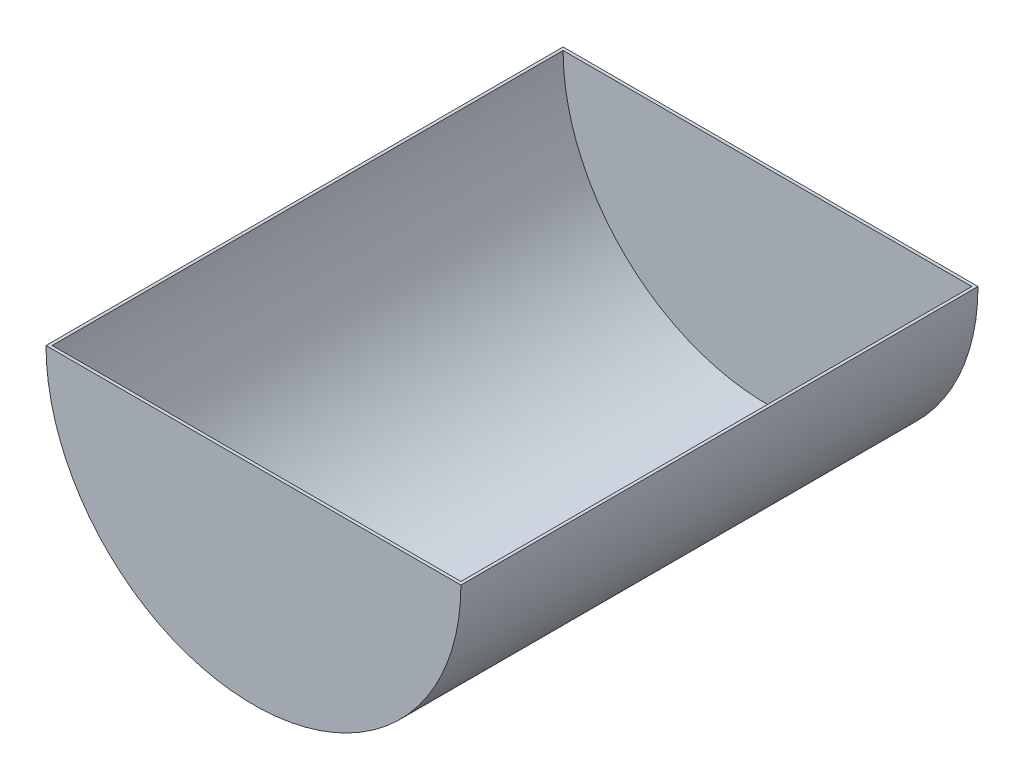
SolidWorks part; units mm, degrees
ref_plane "Front Plane" through (0, 0, 0) normal (0, 0, 1) x (1, 0, 0)
ref_plane "Top Plane" through (0, 0, 0) normal (0, 1, 0) x (1, 0, 0)
ref_plane "Right Plane" through (0, 0, 0) normal (1, 0, 0) x (0, 0, -1)
sketch "Sketch1" plane through (0, 0, 0) normal (0, 0, 1) x (1, 0, 0)
  line L1 (-200, 0) -> (200, 0)
  arc A0 (-200, 0) -> (200, 0) centre (0, 0) ccw
  dimension "D1" = 400
extrude "Boss-Extrude1" add sketch "Sketch1" along normal blind 500
shell "Shell1" thickness 3 removed face at (0, 0, 250) outward yes
